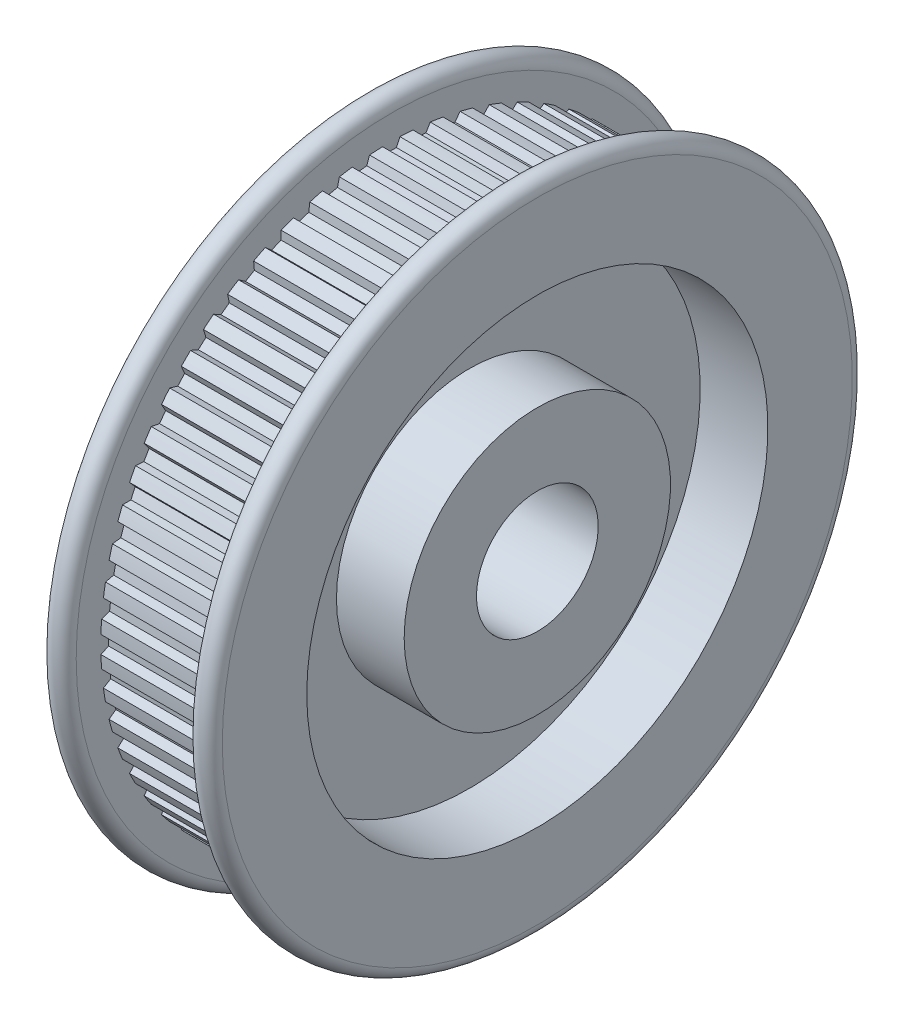
SolidWorks part; units mm, degrees
ref_plane "Front Plane" through (0, 0, 0) normal (0, 0, 1) x (1, 0, 0)
ref_plane "Top Plane" through (0, 0, 0) normal (0, 1, 0) x (1, 0, 0)
ref_plane "Right Plane" through (0, 0, 0) normal (1, 0, 0) x (0, 0, -1)
sketch "Sketch2" plane through (0, 0, 0) normal (1, 0, 0) x (0, 0, -1)
  line L3 (0, 0) -> (0, 18.5745) construction
  line L6 (0, -19.0825) -> (0, -19.4) construction
  line L7 (-0.5715, 19.0739) -> (-0.3372, 18.5714)
  line L8 (0.5715, 19.0739) -> (0.3372, 18.5714)
  line L9 (-0.5715, 19.0739) -> (-0.6445, 19.2305)
  line L10 (0.5715, 19.0739) -> (0.6445, 19.2305)
  line L12 (-0.3372, 18.5714) -> (0.3372, 18.5714)
  line L14 (0, 19.0825) -> (0, 19.4) construction
  line L15 (0, 0) -> (0, -1.143) construction
  circle A0 centre (0, 0) radius 19.4 construction
  circle A1 centre (0, 0) radius 18.5745 construction
  circle A2 centre (0, 0) radius 19.0825 construction
  arc A7 (0.6445, 19.2305) -> (-0.6445, 19.2305) centre (0, 0) ccw
  point P5 (0, 19.2412)
  dimension "D3" = 0.3175
  dimension "D1" = 50
sketch "Sketch1" plane through (0, 0, 0) normal (0, 0, 1) x (1, 0, 0)
  line L0 (-7.9, 0) -> (9.6, 0) construction
  line L1 (-7.9, 4) -> (9.6, 4)
  line L2 (9.6, 4) -> (9.6, 11.49)
  line L3 (9.6, 11.49) -> (8, 11.49)
  line L4 (8, 11.49) -> (8, 19.15)
  line L5 (8, 19.15) -> (0, 19.15)
  line L6 (0, 19.15) -> (0, 20.7)
  line L7 (-1.6, 20.7) -> (-1.6, 8.75)
  line L8 (-1.6, 8.75) -> (-7.9, 8.75)
  line L9 (-7.9, 8.75) -> (-7.9, 4)
  line L10 (8, 19.15) -> (8, 20.7)
  line L11 (9.6, 20.7) -> (9.6, 11.49)
  arc A0 (0, 20.7) -> (-1.6, 20.7) centre (-0.8, 20.7) ccw
  arc A1 (8, 20.7) -> (9.6, 20.7) centre (8.8, 20.7) cw
  dimension "Overall Width" = 17.5
  dimension "For Shaft Dia." = 8
  dimension "Hub Dia." = 17.5
  dimension "OD" = 43
  dimension "Flange Dia." = 38.3
  dimension "D1" = 6.3
  dimension "D2" = 1.6
  dimension "Inside Width" = 8
  dimension "D4" = 22.98
revolve "Revolve1" add sketch "Sketch1" angle 360 mid plane about L0 region at (2.232, 10.6774, 0) region at (8.8, 16.4108, 0)
sketch "Sketch6" plane through (0, 0, 0) normal (0, 0, 1) x (1, 0, 0)
  line L0 (-1.6, 8.75) -> (2.85, 8.75)
  line L1 (2.85, 8.75) -> (2.85, 15.15)
  line L2 (2.85, 15.15) -> (-1.6, 15.15)
  line L3 (-1.6, 20.7) -> (-1.6, 8.75) construction
  line L4 (-1.6, 15.15) -> (-1.6, 8.75)
  line L5 (9.6, 20.7) -> (9.6, 11.49) construction
  line L6 (9.6, 8.75) -> (5.15, 8.75)
  line L7 (9.6, 8.75) -> (9.6, 15.15)
  line L8 (9.6, 15.15) -> (5.15, 15.15)
  line L9 (5.15, 8.75) -> (5.15, 15.15)
  line L10 (-1.6, 0) -> (9.6, 0) construction
  line L11 (-1.6, 8.75) -> (-1.6, -8.75) construction
  line L12 (2.85, 8.75) -> (5.15, 8.75) construction
  line L13 (4, 8.75) -> (4, 0) construction
  line L14 (8, 19.15) -> (0, 19.15) construction
  dimension "D1" = 2.3
  dimension "D2" = 4
revolve "Cut-Revolve1" cut sketch "Sketch6" angle 360 about L10
sketch "Sketch4" plane through (0, 0, 0) normal (1, 0, 0) x (0, 0, -1)
  circle A0 centre (0, 0) radius 19.0825
  circle A1 centre (0, 0) radius 19.0825 construction
  circle A2 centre (0, 0) radius 19.4
  circle A4 centre (0, 0) radius 19.4 construction
extrude "Cut-Extrude2" cut sketch "Sketch4" along normal up to surface (8 mm away) up to face at (8, 0, 20.7)
sketch "Sketch3" plane through (0, 0, 0) normal (1, 0, 0) x (0, 0, -1)
  line L2 (-0.5715, 19.0739) -> (-0.3372, 18.5714) construction
  line L3 (-0.3372, 18.5714) -> (0.3372, 18.5714) construction
  line L4 (0.5715, 19.0739) -> (0.3372, 18.5714) construction
  line L5 (-0.6445, 19.2305) -> (-0.3372, 18.5714)
  line L6 (-0.3372, 18.5714) -> (0.3372, 18.5714)
  line L7 (0.6445, 19.2305) -> (0.3372, 18.5714)
  arc A1 (0.6445, 19.2305) -> (-0.6445, 19.2305) centre (0, 0) ccw construction
  arc A2 (0.6445, 19.2305) -> (-0.6445, 19.2305) centre (0, 0) ccw
extrude "Cut-Extrude1" cut sketch "Sketch3" along normal up to surface (8 mm away) up to face at (8, 0, 19.0825)
pattern_circular "CirPattern1" count 60 over 360 about axis through (-7.9, 0, 0) along (-1, 0, 0) of "Cut-Extrude1"
sketch "Sketch5" plane through (0, 0, 0) normal (0, 0, 1) x (1, 0, 0)
  point P0 (8, 0)
ref_axis "Center Axis 1" through (9.938, 0, 0) along (-1, 0, 0)
ref_plane "Contact Plane 1" through (-7.9, 0, 0) normal (-1, 0, 0) x (0, 0, 1)
ref_plane "Contact Plane 2" through (8, 0, 0) normal (-1, 0, 0) x (0, 0, 1)
equation "\"D3@Sketch2\" = (\"hs@Sketch2\"-\"ht@Sketch2\")/2"
equation "\"D4@Sketch1\"=\"Flange Dia.@Sketch1\"*.6"
